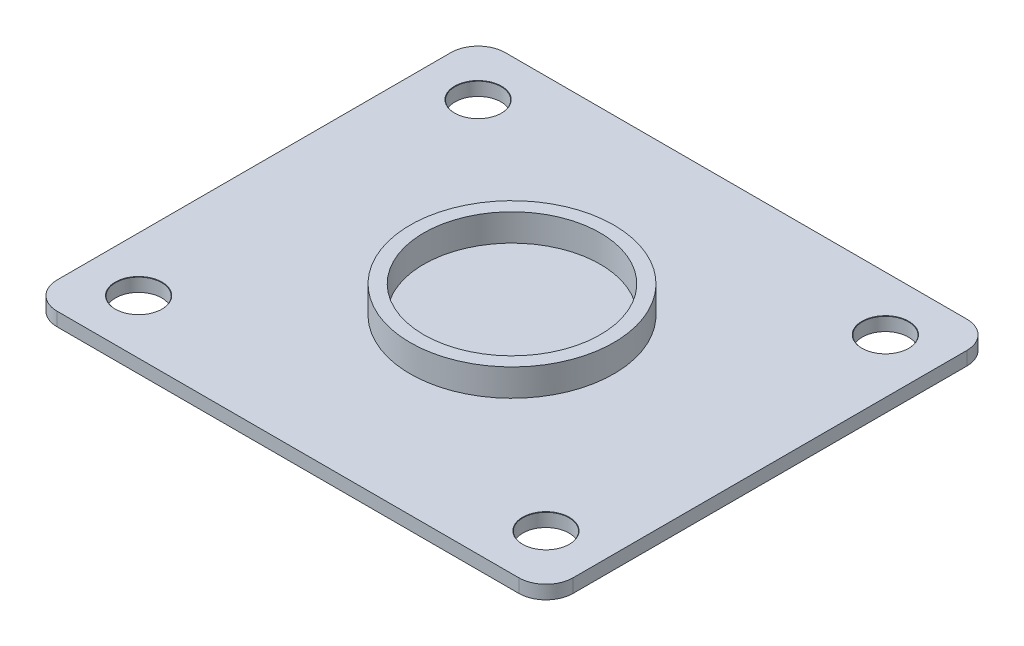
SolidWorks part; units mm, degrees
ref_plane "Front Plane" through (0, 0, 0) normal (0, 0, 1) x (1, 0, 0)
ref_plane "Top Plane" through (0, 0, 0) normal (0, 1, 0) x (1, 0, 0)
ref_plane "Right Plane" through (0, 0, 0) normal (1, 0, 0) x (0, 0, -1)
sketch "Sketch1" plane through (0, 0, 0) normal (0, 1, 0) x (1, 0, 0)
  line L1 (0, 0) -> (38, 0)
  line L2 (0, 0) -> (0, 33)
  line L3 (0, 33) -> (38, 33)
  line L4 (38, 0) -> (38, 33)
  dimension "D1" = 38
  dimension "D2" = 33
extrude "Boss-Extrude1" add sketch "Sketch1" along normal blind 1
sketch "Sketch2" plane through (0, 1, 0) normal (0, 1, 0) x (1, 0, 0)
  line L0 (38, 33) -> (0, 33) construction
  line L1 (0, 33) -> (0, 0) construction
  circle A0 centre (19, 16.5) radius 7.5
  circle A1 centre (19, 16.5) radius 6.5
  point P7 (19, 33)
  point P10 (0, 16.5)
  dimension "D1" = 1
  dimension "D2" = 15
extrude "Boss-Extrude2" add sketch "Sketch2" along normal blind 2
hole_wizard "M3 Clearance Hole1" positions "Sketch3" profile "Sketch4" hole size "M3" standard "ANSI Metric" end condition through all
sketch "Sketch3" plane through (0, 1, 0) normal (0, 1, 0) x (1, 0, 0)
  line L0 (0, 0) -> (38, 0) construction
  line L1 (0, 33) -> (0, 0) construction
  line L2 (19, 0) -> (19, 33) construction
  line L3 (38, 33) -> (0, 33) construction
  line L5 (38, 16.5) -> (0, 16.5) construction
  line L6 (38, 0) -> (38, 33) construction
  line L8 (4, 4) -> (34, 4) construction
  line L9 (4, 29) -> (4, 4) construction
  point P0 (4, 4)
  point P2 (4, 29)
  point P4 (34, 29)
  point P6 (34, 4)
  point P31 (19, 4)
  point P39 (4, 16.5)
  dimension "D1" = 25
  dimension "D2" = 30
sketch "Sketch4" plane through (4, 1, -4) normal (1, 0, 0) x (0, 0, 1)
  line L0 (0, 0) -> (0, 1)
  line L1 (0, 1) -> (1.7, 1)
  line L2 (1.7, 1) -> (1.7, 0.025)
  line L3 (1.7, 0.025) -> (1.725, 0)
  line L5 (1.725, 0) -> (0, 0)
  line L6 (-1.7, 0.025) -> (-1.725, 0) construction
  line L11 (0, -6.35) -> (0, 107.95) construction
  dimension "Thru Hole Dia." = 3.4
  dimension "Thru Hole Depth" = 1
  dimension "Near C'Sink Dia." = 3.45
  dimension "Near C'Sink Angle" = 90
fillet "Fillet1" radius 2 4 edges at (0, 0.5, -33) (38, 0.5, -33) (38, 0.5, 0) (0, 0.5, 0)
